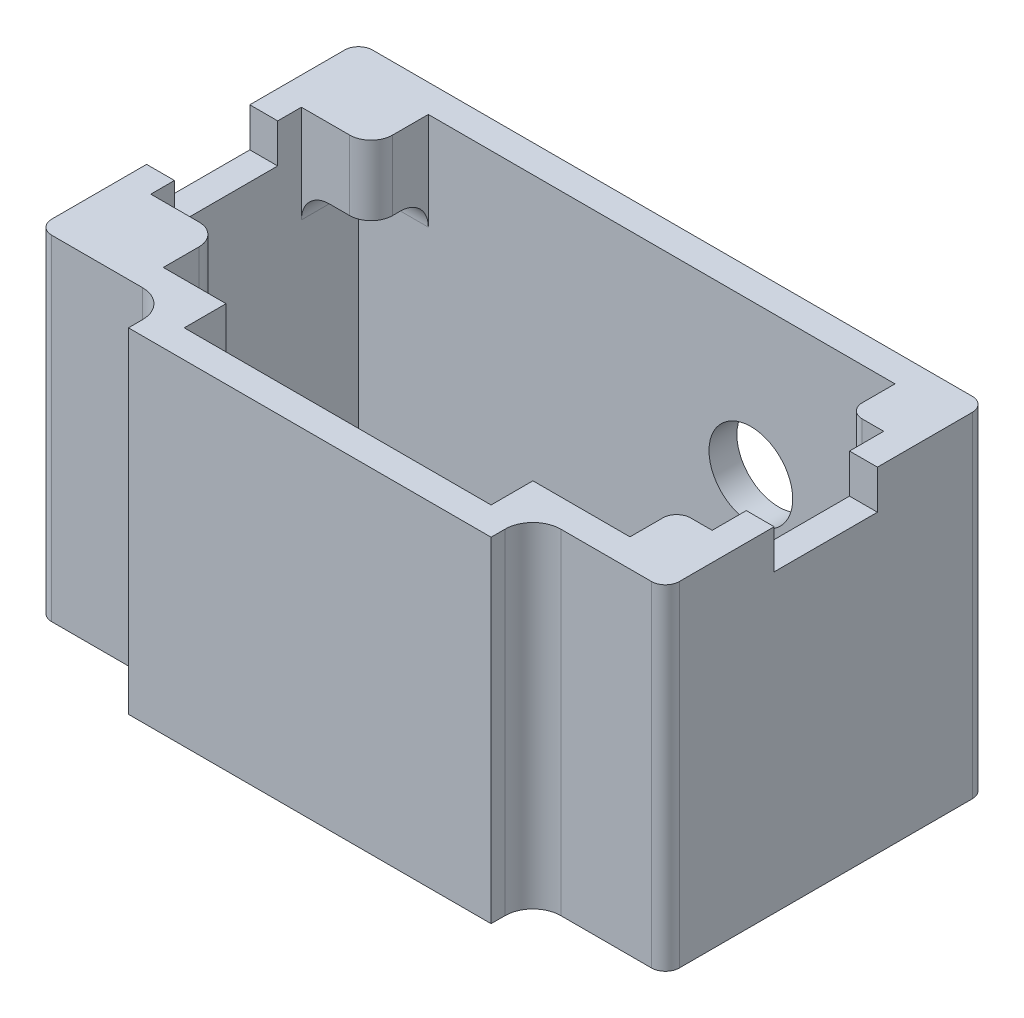
SolidWorks part; units mm, degrees
ref_plane "Front Plane" through (0, 0, 0) normal (0, 0, 1) x (1, 0, 0)
ref_plane "Top Plane" through (0, 0, 0) normal (0, 1, 0) x (1, 0, 0)
ref_plane "Right Plane" through (0, 0, 0) normal (1, 0, 0) x (0, 0, -1)
sketch "Sketch1" plane through (0, 0, 0) normal (0, 1, 0) x (1, 0, 0)
  line L1 (-28.575, -14.605) -> (28.575, -14.605)
  line L2 (-28.575, -14.605) -> (-28.575, 14.605)
  line L3 (-28.575, 14.605) -> (28.575, 14.605)
  line L4 (28.575, -14.605) -> (28.575, 14.605)
  line L5 (-28.575, -14.605) -> (28.575, 14.605) construction
  line L6 (-28.575, 14.605) -> (28.575, -14.605) construction
  point P0 (0, 0)
  dimension "D1" = 57.15
  dimension "D2" = 29.21
extrude "Boss-Extrude1" add sketch "Sketch1" along normal blind 30.48
shell "Shell1" thickness 2.54 removed face at (0, 30.48, 0)
sketch "Sketch2" plane through (0, 0, 0) normal (0, -1, 0) x (1, 0, 0)
  line L0 (0, 0) -> (37.592, 0) construction
  line L1 (28.575, 14.605) -> (28.575, -14.605) construction
  line L2 (24.13, -6.477) -> (13.462, -6.477)
  line L3 (24.13, -6.477) -> (24.13, 6.477)
  line L4 (24.13, 6.477) -> (13.462, 6.477)
  line L5 (13.462, -6.477) -> (13.462, 6.477)
  line L6 (24.13, -6.477) -> (13.462, 6.477) construction
  line L7 (24.13, 6.477) -> (13.462, -6.477) construction
  point P3 (18.796, 0)
  dimension "D1" = 12.954
  dimension "D2" = 10.668
  dimension "D3" = 4.445
extrude "Cut-Extrude1" cut sketch "Sketch2" against normal up to surface (2.54 mm away) up to face at (0, 2.54, 0)
sketch "Sketch3" plane through (0, 30.48, 0) normal (0, 1, 0) x (1, 0, 0)
  line L0 (0, 0) -> (-37.2945, 0) construction
  line L1 (-26.035, 12.065) -> (-26.035, -12.065) construction
  line L17 (-26.035, 12.065) -> (-26.035, 6.858)
  line L19 (-19.685, 12.065) -> (-19.685, 8.8138)
  line L20 (-21.6408, 6.858) -> (-26.035, 6.858)
  line L21 (-19.685, -12.065) -> (-19.685, -8.8138)
  line L22 (-21.6408, -6.858) -> (-26.035, -6.858)
  line L23 (-26.035, -12.065) -> (-26.035, -6.858)
  line L24 (-19.685, -12.065) -> (-26.035, -12.065)
  line L25 (26.035, 12.065) -> (-26.035, 12.065) construction
  line L26 (26.035, 12.065) -> (22.8092, 12.065)
  line L27 (22.8092, 12.065) -> (22.8092, 9.0805)
  line L28 (26.035, 7.8105) -> (26.035, 12.065)
  line L29 (26.035, -12.065) -> (26.035, 12.065) construction
  line L30 (-26.035, 12.065) -> (-19.685, 12.065)
  line L34 (26.035, -12.065) -> (26.035, 12.065) construction
  line L35 (26.035, 7.8105) -> (24.0792, 7.8105)
  line L36 (26.035, -7.8105) -> (26.035, -12.065)
  line L37 (26.035, -12.065) -> (22.8092, -12.065)
  line L38 (22.8092, -12.065) -> (22.8092, -9.0805)
  line L39 (26.035, -7.8105) -> (24.0792, -7.8105)
  arc A6 (-19.685, 8.8138) -> (-21.6408, 6.858) centre (-21.6408, 8.8138) cw
  arc A7 (-19.685, -8.8138) -> (-21.6408, -6.858) centre (-21.6408, -8.8138) ccw
  arc A10 (22.8092, 9.0805) -> (24.0792, 7.8105) centre (24.0792, 9.0805) ccw
  arc A11 (22.8092, -9.0805) -> (24.0792, -7.8105) centre (24.0792, -9.0805) cw
  dimension "D2" = 13.716
  dimension "D3" = 1.9558
  dimension "D5" = 1.27
  dimension "D1" = 6.35
  dimension "D4" = 15.621
  dimension "D6" = 45.72
extrude "Boss-Extrude2" add sketch "Sketch3" against normal blind 6.35
sketch "Sketch4" plane through (-28.575, 0, 0) normal (-1, 0, 0) x (0, 0, 1)
  line L0 (-14.605, 30.48) -> (14.605, 30.48) construction
  line L1 (-14.605, 30.48) -> (14.605, 30.48) construction
  line L3 (-4.699, 26.924) -> (4.699, 26.924)
  line L4 (-4.699, 26.924) -> (-4.699, 34.036)
  line L5 (-4.699, 34.036) -> (4.699, 34.036)
  line L6 (4.699, 26.924) -> (4.699, 34.036)
  line L7 (-4.699, 26.924) -> (4.699, 34.036) construction
  line L8 (-4.699, 34.036) -> (4.699, 26.924) construction
  point P2 (0, 30.48)
  dimension "D1" = 9.398
  dimension "D2" = 3.556
extrude "Cut-Extrude2" cut sketch "Sketch4" against normal up to surface (57.15 mm away) contours L4 L3 L6 L5 up to face at (28.575, 15.24, 0)
sketch "Sketch6" plane through (0, 30.48, 0) normal (0, 1, 0) x (1, 0, 0)
  line L0 (-28.575, -14.605) -> (28.575, -14.605) construction
  line L5 (-16.51, -14.605) -> (16.51, -14.605)
  line L6 (-16.51, -14.605) -> (-16.51, -18.415)
  line L7 (-16.51, -18.415) -> (16.51, -18.415)
  line L8 (16.51, -18.415) -> (16.51, -14.605)
  line L9 (0, 0) -> (0, -27.7045) construction
  point P9 (0, -14.605)
  dimension "D1" = 3.81
  dimension "D2" = 33.02
extrude "Boss-Extrude3" add sketch "Sketch6" against normal up to surface (30.48 mm away) up to face at (18.796, 0, 0)
sketch "Sketch7" plane through (0, 30.48, 0) normal (0, 1, 0) x (1, 0, 0)
  line L0 (-16.51, -18.415) -> (16.51, -18.415) construction
  line L1 (-19.685, -12.065) -> (22.8092, -12.065) construction
  line L2 (-16.51, -18.415) -> (16.51, -18.415)
  line L3 (-13.97, -12.065) -> (13.97, -12.065)
  line L4 (-13.97, -12.065) -> (-13.97, -15.875)
  line L5 (-13.97, -15.875) -> (13.97, -15.875)
  line L6 (13.97, -15.875) -> (13.97, -12.065)
  line L7 (-16.51, -14.605) -> (-16.51, -18.415) construction
  line L8 (16.51, -18.415) -> (16.51, -14.605) construction
  line M29 (22.8092, -12.065) -> (-19.685, -12.065)
  dimension "D1" = 2.54
  dimension "D2" = 2.54
  dimension "D3" = 2.54
extrude "Cut-Extrude3" cut sketch "Sketch7" against normal offset from surface (27.94 mm away) 2.54 contours L5 L6 L4 M29 region at (0, 30.48, 13.97) up to face at (18.796, 0, 0)
fillet "Fillet1" radius 2.54 2 edges at (16.51, 15.24, 14.605) (-16.51, 15.24, 14.605)
fillet "Fillet2" radius 1.27 4 edges at (28.575, 15.24, 14.605) (28.575, 15.24, -14.605) (-28.575, 15.24, -14.605) (-28.575, 15.24, 14.605)
sketch "Sketch8" plane through (0, 0, -14.605) normal (0, 0, -1) x (-1, 0, 0)
  circle A0 centre (-9.6841, 16.7451) radius 3.81
  dimension "D1" = 7.62
extrude "Cut-Extrude4" cut sketch "Sketch8" against normal up to surface (2.54 mm away) up to face at (0.781, 20.32, -12.065)
fillet "Fillet3" radius 2.54 8 edges at (-26.035, 24.13, 9.4615) (-22.86, 24.13, 12.065) (24.4221, 24.13, 12.065) (26.035, 24.13, 9.9377) (-22.86, 24.13, -12.065) (-26.035, 24.13, -9.4615) (24.4221, 24.13, -12.065) (26.035, 24.13, -9.9378)
